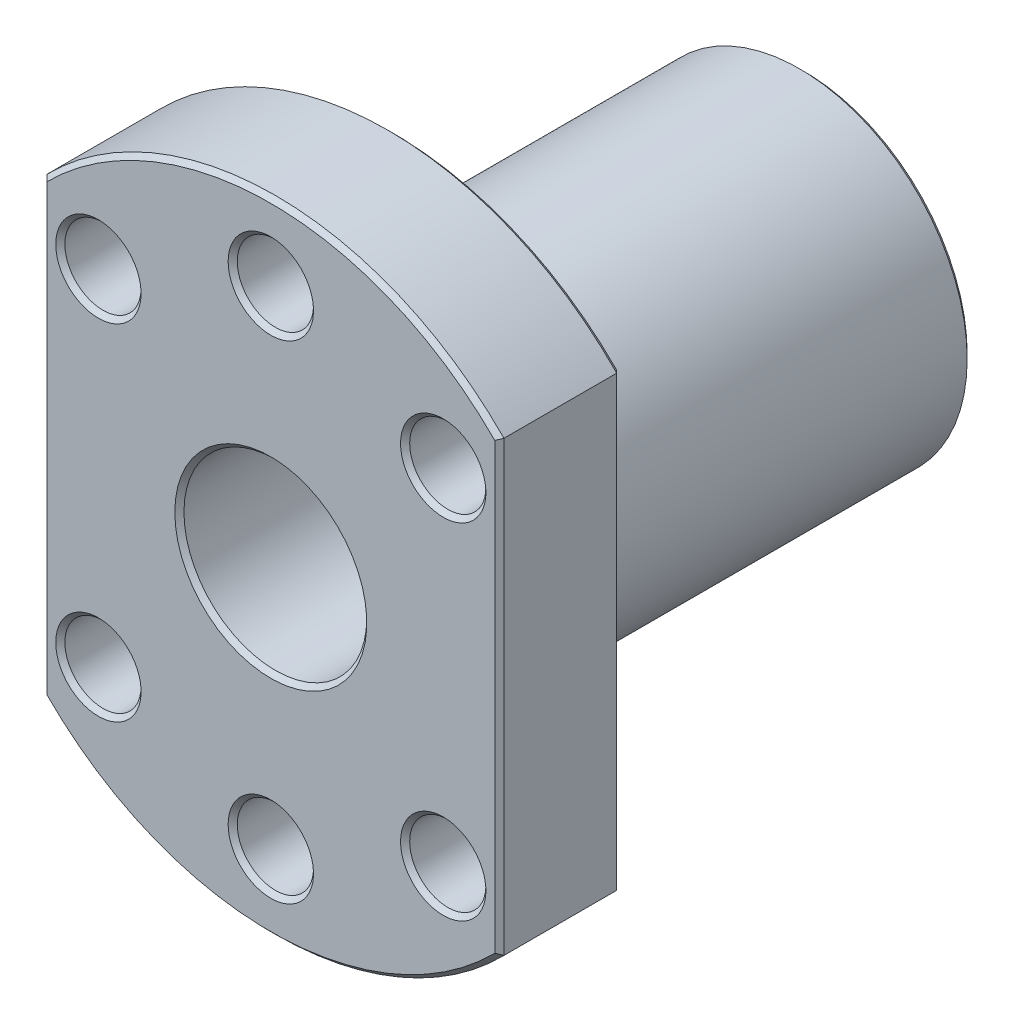
SolidWorks part; units mm, degrees
ref_plane "Front Plane" through (0, 0, 0) normal (0, 0, 1) x (1, 0, 0)
ref_plane "Top Plane" through (0, 0, 0) normal (0, 1, 0) x (1, 0, 0)
ref_plane "Right Plane" through (0, 0, 0) normal (1, 0, 0) x (0, 0, -1)
sketch "Sketch1" plane through (0, 0, 0) normal (1, 0, 0) x (0, 0, -1)
  line L0 (-27, 0) -> (-1.1455, 0) construction
  line L1 (17.5, 6) -> (-17.5, 6)
  line L2 (-17.5, 6) -> (-17.5, 21)
  line L3 (-17.5, 21) -> (-9.5, 21)
  line L4 (-9.5, 21) -> (-9.5, 11)
  line L5 (-9.5, 11) -> (17.5, 11)
  line L6 (17.5, 11) -> (17.5, 6)
  line L7 (0, 6) -> (0, 0) construction
  dimension "D1" = 27
  dimension "D2" = 8
  dimension "D3" = 21
  dimension "D4" = 12
  dimension "D5" = 22
revolve "Revolve1" add sketch "Sketch1" angle 360 about L0
sketch "Sketch2" plane through (0, 0, 0) normal (0, 1, 0) x (1, 0, 0)
  line L0 (-21, -17.5) -> (21, -17.5) construction
  line L1 (-21, -9.5) -> (-15, -9.5)
  line L2 (-21, -9.5) -> (-21, -17.5)
  line L3 (-21, -17.5) -> (-15, -17.5)
  line L4 (-15, -9.5) -> (-15, -17.5)
  line L6 (21, -9.5) -> (15, -9.5)
  line L7 (21, -9.5) -> (21, -17.5)
  line L8 (21, -17.5) -> (15, -17.5)
  line L9 (15, -9.5) -> (15, -17.5)
  dimension "D1" = 30
extrude "Cut-Extrude1" cut sketch "Sketch2" against normal through all both and the other way through all
sketch "Sketch3" plane through (0, 0, 17.5) normal (0, 0, 1) x (1, 0, 0)
  line L0 (0, 16) -> (0, 0) construction
  circle A0 centre (0, 16) radius 2.5
  circle A1 centre (11.3137, 11.3137) radius 2.5
  circle A2 centre (16, 0) radius 2.5 construction
  circle A3 centre (11.3137, -11.3137) radius 2.5
  circle A4 centre (0, -16) radius 2.5
  circle A5 centre (-11.3137, -11.3137) radius 2.5
  circle A6 centre (-16, 0) radius 2.5 construction
  circle A7 centre (-11.3137, 11.3137) radius 2.5
  point P19 (0, 0)
  dimension "D2" = 5
  dimension "D1" = 16
  dimension "D3" = 8
extrude "Cut-Extrude2" cut sketch "Sketch3" against normal blind 10
chamfer "Chamfer1" distance 0.3 angle 45 24 edges at (11, 0, 9.5) (-15, 0, 9.5) (0, -21, 9.5) (15, 0, 9.5) (0, 21, 9.5) (2.5, 16, 9.5) (-8.8137, 11.3137, 9.5) (-8.8137, -11.3137, 9.5) (2.5, -16, 9.5) (13.8137, -11.3137, 9.5) (13.8137, 11.3137, 9.5) (-15, 0, 17.5) (0, 21, 17.5) (15, 0, 17.5) (0, -21, 17.5) (6, 0, 17.5) (2.5, 16, 17.5) (-8.8137, 11.3137, 17.5) (-8.8137, -11.3137, 17.5) (2.5, -16, 17.5) (13.8137, -11.3137, 17.5) (13.8137, 11.3137, 17.5) (6, 0, -17.5) (11, 0, -17.5)
sketch "Sketch4" [suppressed] plane through (0, 0, 0) normal (1, 0, 0) x (0, 0, -1)
  line L0 (0, 0) -> (0, 11) construction
  line L1 (22, 11) -> (12, 11)
  line L2 (-22, 11) -> (-22, 24)
  line L3 (-22, 24) -> (-12, 24)
  line L4 (-12, 24) -> (-12, 14)
  line L5 (-12, 14) -> (22, 14)
  line L6 (22, 14) -> (22, 11)
  line L7 (-17.9283, 0) -> (16.6653, 0) construction
  line L8 (-12, 11) -> (-22, 11)
  line L9 (-12, 11) -> (12, 11) construction
  line L10 (-12, 11) -> (-12, 8)
  line L11 (-12, 8) -> (12, 8)
  line L12 (12, 11) -> (12, 8)
  dimension "D1" = 24
  dimension "D2" = 28
  dimension "D3" = 10
  dimension "D4" = 34
  dimension "D5" = 22
  dimension "D6" = 22
  dimension "D7" = 8
  dimension "D8" = 10
revolve "Revolve2" [suppressed] add sketch "Sketch4" angle 360 about L7
sketch "Sketch5" [suppressed] plane through (0, 0, 22) normal (0, 0, 1) x (1, 0, 0)
  line L0 (0, 35.9904) -> (0, 19.305) construction
  line L1 (-28.3026, 0) -> (22.4371, 0) construction
  line L2 (20, 20) -> (-20, 20)
  line L3 (20, 20) -> (20, 30)
  line L4 (20, 30) -> (-20, 30)
  line L5 (-20, 20) -> (-20, 30)
  line L6 (20, 20) -> (-20, 30) construction
  line L7 (20, 30) -> (-20, 20) construction
  line L8 (20, -20) -> (20, -30)
  line L9 (20, -20) -> (-20, -20)
  line L10 (-20, -20) -> (-20, -30)
  line L11 (20, -30) -> (-20, -30)
  point P1 (0, 25)
  dimension "D1" = 40
  dimension "D2" = 20
  dimension "D3" = 10
extrude "Cut-Extrude3" [suppressed] cut sketch "Sketch5" against normal through all
sketch "Sketch6" [suppressed] plane through (0, 0, 22) normal (0, 0, 1) x (1, 0, 0)
  line L0 (0, 0) -> (-19, 0) construction
  circle A0 centre (-19, 0) radius 2.75
  circle A1 centre (-13.435, 13.435) radius 2.75
  circle A2 centre (0, 19) radius 2.75 construction
  circle A3 centre (13.435, 13.435) radius 2.75
  circle A4 centre (19, 0) radius 2.75
  circle A5 centre (13.435, -13.435) radius 2.75
  circle A6 centre (0, -19) radius 2.75 construction
  circle A7 centre (-13.435, -13.435) radius 2.75
  point P20 (0, 0)
  dimension "D1" = 5.5
  dimension "D2" = 19
  dimension "D3" = 8
extrude "Cut-Extrude4" [suppressed] cut sketch "Sketch6" against normal through all
sketch "Sketch7" [suppressed] plane through (0, 20, 0) normal (0, 1, 0) x (1, 0, 0)
  line L0 (0, 0) -> (0, -18) construction
  line L1 (0, 0) -> (-14, 0) construction
  line L2 (-14, 22) -> (-14, -12) construction
  circle A0 centre (0, -18) radius 1.5
  circle A1 centre (0, 18) radius 1.5
  dimension "D1" = 3
  dimension "D2" = 18
extrude "Cut-Extrude5" [suppressed] cut sketch "Sketch7" against normal through all
ref_plane "Plane1" [suppressed] through (13.6768, 5.6651, 0) normal (0.9239, 0.3827, 0) x (0, 0, -1)
sketch "Sketch8" [suppressed] plane through (13.6768, 5.6651, 0) normal (0.9239, 0.3827, 0) x (0, 0, -1)
  line L0 (-12, 0) -> (-22, 0) construction
  line L2 (0, 0) -> (-17, 0) construction
  line L3 (-22, 13.4007) -> (-22, -23.5545) construction
  line L4 (-12, -14) -> (-12, 14) construction
  circle A0 centre (-17, 0) radius 2.5
  dimension "D1" = 5
extrude "Cut-Extrude6" [suppressed] cut sketch "Sketch8" against normal blind 10 and the other way through all
sketch "Sketch9" [suppressed] plane through (13.6768, 5.6651, 0) normal (0.9239, 0.3827, 0) x (0, 0, -1)
  circle A0 centre (-17, 0) radius 3
  dimension "D1" = 6
extrude "Cut-Extrude7" [suppressed] cut sketch "Sketch9" along normal through all
chamfer "Chamfer2" [suppressed] distance 0.5 angle 45
other "DeleteFace1" [suppressed]
